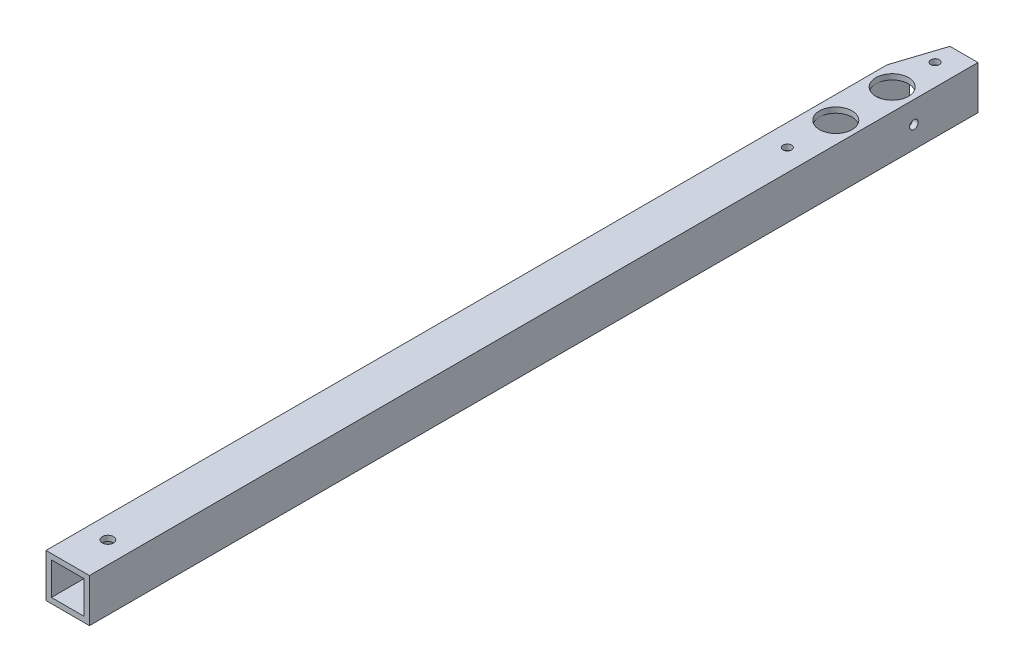
SolidWorks part; units mm, degrees
ref_plane "Front Plane" through (0, 0, 0) normal (0, 0, 1) x (1, 0, 0)
ref_plane "Top Plane" through (0, 0, 0) normal (0, 1, 0) x (1, 0, 0)
ref_plane "Right Plane" through (0, 0, 0) normal (1, 0, 0) x (0, 0, -1)
sketch "Sketch1" plane through (0, 0, 0) normal (0, 0, 1) x (1, 0, 0)
  line L0 (-9.525, 9.525) -> (9.525, 9.525)
  line L2 (-12.7, 12.7) -> (12.7, 12.7)
  line L3 (-12.7, 12.7) -> (-12.7, -12.7)
  line L4 (-12.7, -12.7) -> (12.7, -12.7)
  line L5 (12.7, 12.7) -> (12.7, -12.7)
  line L10 (9.525, 9.525) -> (9.525, -9.525)
  line L11 (-9.525, -9.525) -> (9.525, -9.525)
  line L12 (-9.525, 9.525) -> (-9.525, -9.525)
  point P12 (0, 12.7)
  point P14 (12.7, 0)
  dimension "Wall Thickness" = 3.175
  dimension "Outside Width" = 25.4
  dimension "Outside Height" = 25.4
  dimension "Inside Height" = 19.05
  dimension "Inside Width" = 19.05
sketch "Sketch2" plane through (0, 0, 0) normal (1, 0, 0) x (0, 0, -1)
  line L0 (266.7, 0) -> (-266.7, 0)
  point P4 (0, 0)
  point P7 (-266.7, 0)
  point P10 (266.7, 0)
  dimension "Length" = 533.4
sketch "Sketch3" plane through (0, 0, 0) normal (0, 0, 1) x (1, 0, 0)
  line L21 (12.7, 12.7) -> (-12.7, 12.7)
  line L22 (12.7, -12.7) -> (12.7, 12.7)
  line L23 (-12.7, -12.7) -> (12.7, -12.7)
  line L24 (-12.7, 12.7) -> (-12.7, -12.7)
  line L25 (12.7, 12.7) -> (-12.7, 12.7)
  line L26 (12.7, -12.7) -> (12.7, 12.7)
  line L27 (-12.7, -12.7) -> (12.7, -12.7)
  line L28 (-12.7, 12.7) -> (-12.7, -12.7)
  line L29 (9.525, 9.525) -> (-9.525, 9.525)
  line L30 (9.525, -9.525) -> (9.525, 9.525)
  line L31 (-9.525, -9.525) -> (9.525, -9.525)
  line L32 (-9.525, 9.525) -> (-9.525, -9.525)
  line L33 (9.525, 9.525) -> (-9.525, 9.525)
  line L34 (9.525, -9.525) -> (9.525, 9.525)
  line L35 (-9.525, -9.525) -> (9.525, -9.525)
  line L36 (-9.525, 9.525) -> (-9.525, -9.525)
  dimension "D1" = 0
  dimension "D2" = 0
extrude "Boss-Extrude1" add sketch "Sketch3" along normal up to vertex (266.7 mm away) and the other way up to vertex (266.7 mm away) up to point (0, 0, 266.7) other way up to point (0, 0, -266.7)
sketch "Drawing Reference" plane through (0, 0, 0) normal (1, 0, 0) x (0, 0, -1)
  line L0 (-266.7, 0) -> (266.7, 0) construction
  line L1 (0, -12.7) -> (0, 12.7) construction
  line L2 (-266.7, -12.7) -> (266.7, -12.7) construction
  line L5 (-266.7, 12.7) -> (266.7, 12.7) construction
  point P7 (-248.412, 0)
  point P8 (248.412, 0)
  dimension "D1" = 18.288
sketch "Sketch4" plane through (0, 12.7, 0) normal (0, 1, 0) x (1, 0, 0)
  line L1 (0, 266.7) -> (0, 215.265) construction
  line L7 (-12.7, 225.0135) -> (-12.7, 266.7)
  line L8 (-188.9197, -317.3351) -> (4.6184, 278.3139) construction
  line L10 (-12.7, -266.7) -> (-12.7, 266.7) construction
  line L11 (-12.7, 266.7) -> (12.7, 266.7)
  line L12 (12.7, 266.7) -> (12.7, 252.73)
  line L13 (12.7, -266.7) -> (12.7, 266.7) construction
  line L14 (12.7, 252.73) -> (-3.6943, 252.73)
  line L15 (-3.6943, 252.73) -> (-12.7, 225.0135)
  circle A0 centre (0, 215.265) radius 9.525
  dimension "D1" = 13.97
  dimension "D2" = 51.435
extrude "Cut-Extrude1" cut sketch "Sketch4" against normal blind 25.4
sketch "Sketch5" plane through (0, 12.7, 0) normal (0, -1, 0) x (1, 0, 0)
  circle A0 centre (0.3539, -181.928) radius 9.525
extrude "Cut-Extrude2" cut sketch "Sketch5" along normal blind 3.175
sketch "Sketch6" plane through (12.7, 0, 0) normal (1, 0, 0) x (0, 0, -1)
  line L0 (252.73, 0) -> (215.265, 0) construction
  line L1 (252.73, -12.7) -> (252.73, 12.7) construction
  dimension "D1" = 37.465
hole_wizard "#10 Clearance Hole1" positions "Sketch7" profile "Sketch8" hole size "#10" standard "ANSI Inch" end condition through all
sketch "Sketch7" plane through (12.7, 0, 0) normal (1, 0, 0) x (0, 0, -1)
  point P0 (215.265, 0)
sketch "Sketch8" plane through (12.7, 0, -215.265) normal (0, 1, 0) x (0, 0, -1)
  line L0 (0, 0) -> (0, 25.4)
  line L1 (0, 25.4) -> (2.4892, 25.4)
  line L2 (2.4892, 25.4) -> (2.4892, 0)
  line L5 (2.4892, 0) -> (0, 0)
  line L11 (0, -6.35) -> (0, 107.95) construction
  dimension "Thru Hole Dia." = 4.9784
  dimension "Thru Hole Depth" = 25.4
hole_wizard "#10 Clearance Hole2" positions "Sketch9" profile "Sketch10" hole size "#10" standard "ANSI Inch" end condition through all
sketch "Sketch9" plane through (0, -12.7, 0) normal (0, -1, 0) x (-1, 0, 0)
  point P0 (0, 153.96)
  point P3 (0, 240.3465)
sketch "Sketch10" plane through (0, -12.7, -153.96) normal (1, 0, 0) x (0, 0, -1)
  line L0 (0, 0) -> (0, 25.4)
  line L1 (0, 25.4) -> (2.4892, 25.4)
  line L2 (2.4892, 25.4) -> (2.4892, 0)
  line L5 (2.4892, 0) -> (0, 0)
  line L11 (0, -6.35) -> (0, 107.95) construction
  dimension "Thru Hole Dia." = 4.9784
  dimension "Thru Hole Depth" = 25.4
hole_wizard "1/4 Clearance Hole1" positions "Sketch11" profile "Sketch12" hole size "1/4" standard "ANSI Inch" end condition through all
sketch "Sketch11" plane through (0, -12.7, 0) normal (0, -1, 0) x (-1, 0, 0)
  point P0 (0, -243.2272)
sketch "Sketch12" plane through (0, -12.7, 243.2272) normal (1, 0, 0) x (0, 0, -1)
  line L0 (0, 0) -> (0, 25.4)
  line L1 (0, 25.4) -> (3.2639, 25.4)
  line L2 (3.2639, 25.4) -> (3.2639, 0)
  line L5 (3.2639, 0) -> (0, 0)
  line L11 (0, -6.35) -> (0, 107.95) construction
  dimension "Thru Hole Dia." = 6.5278
  dimension "Thru Hole Depth" = 25.4
equation "\"D1@Drawing Reference\"=\"Outside Width@Sketch1\" * 0.72"
